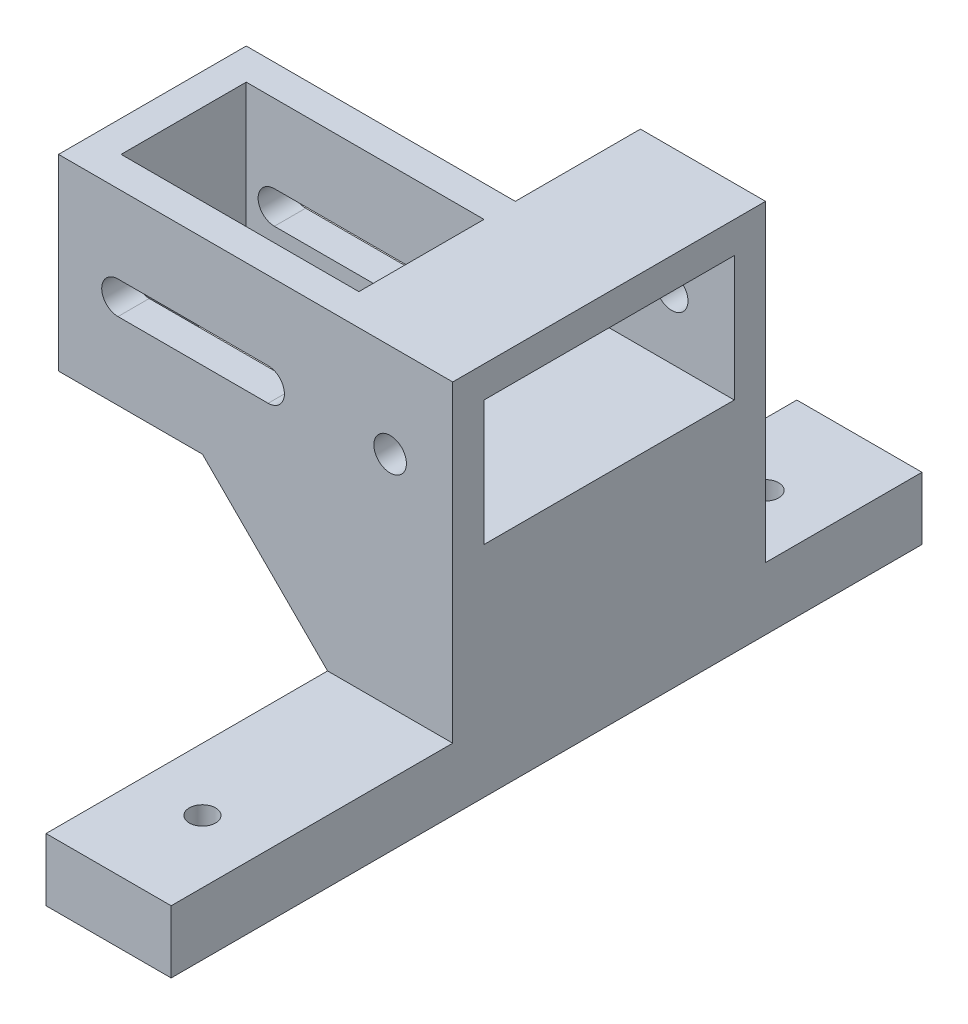
SolidWorks part; units mm, degrees
ref_plane "Front Plane" through (0, 0, 0) normal (0, 0, 1) x (1, 0, 0)
ref_plane "Top Plane" through (0, 0, 0) normal (0, 1, 0) x (1, 0, 0)
ref_plane "Right Plane" through (0, 0, 0) normal (1, 0, 0) x (0, 0, -1)
sketch "Sketch4" plane through (0, 0, 0) normal (0, 1, 0) x (1, 0, 0)
  line L1 (0, 0) -> (20, 0)
  line L2 (0, 0) -> (0, 120)
  line L3 (0, 120) -> (20, 120)
  line L4 (20, 0) -> (20, 120)
  dimension "D1" = 120
  dimension "D2" = 20
extrude "Boss-Extrude4" add sketch "Sketch4" along normal blind 10
sketch "Sketch5" plane through (0, 10, 0) normal (0, 1, 0) x (1, 0, 0)
  line L0 (10, 0) -> (10, 15) construction
  line L1 (0, 0) -> (20, 0) construction
  line L2 (10, 15) -> (10, 105) construction
  circle A0 centre (10, 105) radius 2.1
  circle A1 centre (10, 15) radius 2.1
  dimension "D3" = 4.2
  dimension "D4" = 4.2
  dimension "D1" = 15
  dimension "D2" = 90
extrude "Cut-Extrude1" cut sketch "Sketch5" against normal up to surface (10 mm away) up to face at (10, 0, -60)
sketch "Sketch6" plane through (0, 10, 0) normal (0, 1, 0) x (1, 0, 0)
  line L1 (0, 95) -> (20, 95)
  line L2 (0, 95) -> (0, 45)
  line L3 (0, 45) -> (20, 45)
  line L4 (20, 95) -> (20, 45)
  line L6 (0, 120) -> (0, 0) construction
  line L7 (20, 0) -> (20, 120) construction
  line L8 (20, 120) -> (0, 120) construction
  dimension "D1" = 50
  dimension "D2" = 20
  dimension "D3" = 25
extrude "Boss-Extrude5" add sketch "Sketch6" along normal blind 50
sketch "Sketch7" plane through (0, 0, 0) normal (-1, 0, 0) x (0, 0, 1)
  line L0 (-45, 60) -> (-45, 10) construction
  line L1 (-50, 35) -> (-90, 35)
  line L2 (-50, 35) -> (-50, 55)
  line L3 (-50, 55) -> (-90, 55)
  line L4 (-90, 35) -> (-90, 55)
  line L5 (-95, 60) -> (-45, 60) construction
  dimension "D1" = 20
  dimension "D2" = 40
  dimension "D3" = 5
  dimension "D4" = 5
extrude "Cut-Extrude2" cut sketch "Sketch7" against normal up to surface (20 mm away) up to face at (20, 20, -65)
sketch "Sketch8" plane through (0, 0, -90) normal (0, 0, 1) x (1, 0, 0)
  line L0 (0, 45) -> (20, 45) construction
  line L1 (0, 55) -> (0, 35) construction
  line L2 (20, 35) -> (20, 55) construction
  circle A0 centre (10, 45) radius 2.6
  dimension "D1" = 5.2
extrude "Cut-Extrude3" cut sketch "Sketch8" against normal mid plane 100
sketch "Sketch9" plane through (0, 0, 0) normal (-1, 0, 0) x (0, 0, 1)
  line L0 (-50, 60) -> (-50, 30)
  line L5 (-50, 30) -> (-45, 30)
  line L6 (-95, 60) -> (-45, 60) construction
  line L7 (-75, 60) -> (-70, 60)
  line L8 (-120, 0) -> (0, 0)
  line L9 (0, 0) -> (0, 10)
  line L10 (0, 10) -> (-45, 10)
  line L11 (-45, 10) -> (-45, 60)
  line L12 (-45, 60) -> (-95, 60)
  line L13 (-95, 60) -> (-95, 10)
  line L14 (-95, 10) -> (-120, 10)
  line L15 (-120, 10) -> (-120, 0)
  line L19 (-45, 30) -> (-45, 60)
  line L20 (-45, 60) -> (-50, 60)
  line L24 (-75, 60) -> (-75, 30)
  line L25 (-75, 30) -> (-70, 30)
  line L26 (-70, 60) -> (-70, 30)
  dimension "D2" = 30
  dimension "D3" = 30
  dimension "D4" = 5
  dimension "D5" = 20
  dimension "D1" = 0
extrude "Boss-Extrude6" add sketch "Sketch9" along normal blind 40
sketch "Sketch10" plane through (0, 0, -75) normal (0, 0, -1) x (-1, 0, 0)
  line L0 (33.5, 44.9) -> (9.5, 44.9) construction
  line L1 (33.5, 42.3) -> (9.5, 42.3)
  line L2 (33.5, 47.5) -> (9.5, 47.5)
  line L3 (40, 60) -> (40, 30) construction
  line L4 (40, 60) -> (0, 60) construction
  arc A0 (33.5, 42.3) -> (33.5, 47.5) centre (33.5, 44.9) ccw
  arc A1 (9.5, 47.5) -> (9.5, 42.3) centre (9.5, 44.9) ccw
  point P2 (21.5, 44.9)
  dimension "D1" = 5.2
  dimension "D2" = 6.5
  dimension "D3" = 24
  dimension "D4" = 15.1
extrude "Cut-Extrude4" cut sketch "Sketch10" against normal blind 40
sketch "Sketch11" plane through (0, 0, -75) normal (0, 0, -1) x (-1, 0, 0)
  line L0 (40, 60) -> (0, 60) construction
  line L1 (38, 60) -> (43, 60)
  line L2 (38, 60) -> (38, 30)
  line L3 (38, 30) -> (43, 30)
  line L4 (43, 60) -> (43, 30)
  line L5 (40, 60) -> (40, 30) construction
  dimension "D1" = 30
  dimension "D2" = 5
  dimension "D3" = 2
extrude "Boss-Extrude7" add sketch "Sketch11" against normal up to surface (30 mm away) up to face at (-21.5, 44.9, -45)
sketch "Sketch12" plane through (-43, 0, 0) normal (-1, 0, 0) x (0, 0, 1)
  line L0 (-60, 60) -> (-60, 30) construction
  line L1 (-45, 60) -> (-75, 60) construction
  line L2 (-45, 30) -> (-75, 30) construction
  circle A0 centre (-60, 45) radius 2.1
  dimension "D1" = 4.2
extrude "Cut-Extrude5" cut sketch "Sketch12" against normal blind 5
chamfer "Chamfer1" distance 20 angle 45 2 edges at (0, 30, -47.5) (0, 30, -72.5)
